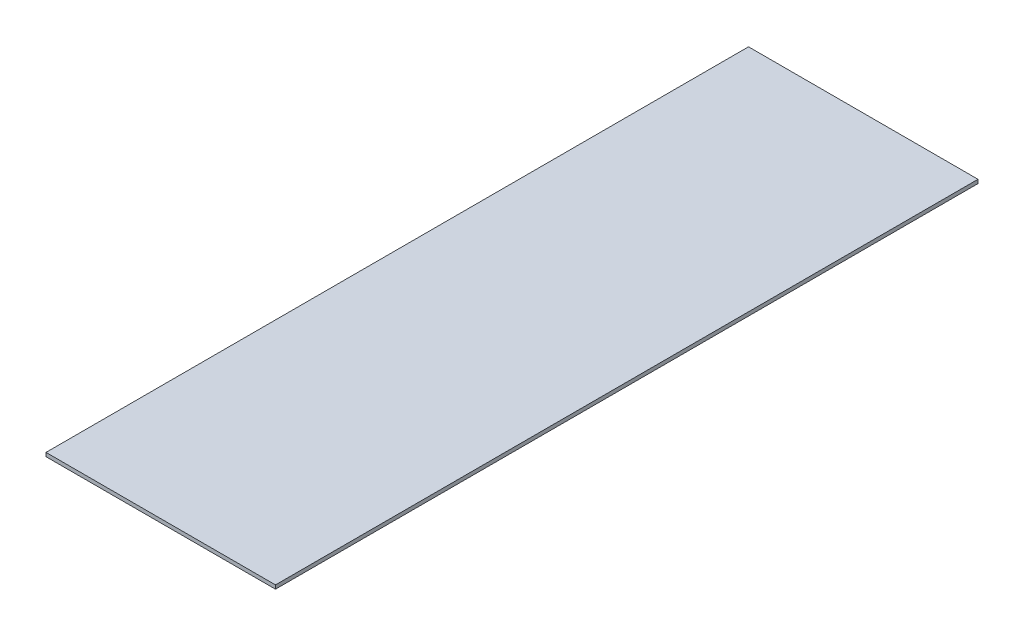
SolidWorks part; units mm, degrees
ref_plane "Front" through (0, 0, 0) normal (0, 0, 1) x (1, 0, 0)
ref_plane "Top" through (0, 0, 0) normal (0, 1, 0) x (1, 0, 0)
ref_plane "Right" through (0, 0, 0) normal (1, 0, 0) x (0, 0, -1)
sketch "Esquisse1" plane through (0, 0, 0) normal (0, 1, 0) x (1, 0, 0)
  line L1 (0, 0) -> (980, 0)
  line L2 (0, 0) -> (0, 3000)
  line L3 (0, 3000) -> (980, 3000)
  line L4 (980, 0) -> (980, 3000)
  dimension "D1" = 980
  dimension "D2" = 3000
extrude "Boss.-Extru.1" add sketch "Esquisse1" along normal blind 16
